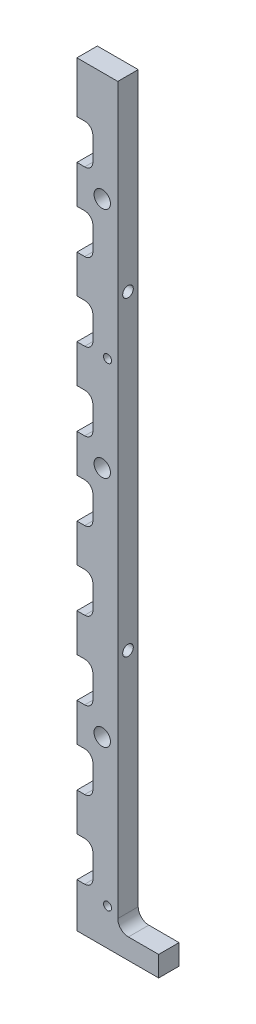
SolidWorks part; units mm, degrees
ref_plane "Front Plane" through (0, 0, 0) normal (0, 0, 1) x (1, 0, 0)
ref_plane "Top Plane" through (0, 0, 0) normal (0, 1, 0) x (1, 0, 0)
ref_plane "Right Plane" through (0, 0, 0) normal (1, 0, 0) x (0, 0, -1)
sketch "Sketch1" plane through (0, 0, 0) normal (0, 0, 1) x (1, 0, 0)
  line L0 (55, 0) -> (-55, 0) construction
  line L1 (-38.1, 0) -> (-50.8, 0)
  line L2 (-38.1, 0) -> (-38.1, 234.95)
  line L3 (-38.1, 234.95) -> (-50.8, 234.95)
  line L4 (-50.8, 0) -> (-50.8, 234.95)
  line L6 (0, -884.6258) -> (0, 49115.3742) construction
  dimension "D1" = 101.6
  dimension "D2" = 12.7
  dimension "D3" = 234.95
extrude "Boss-Extrude1" add sketch "Sketch1" along normal mid plane 6.35
sketch "Sketch2" plane through (0, 0, 0) normal (0, 0, 1) x (1, 0, 0)
  line L0 (-50.8, 234.95) -> (-50.8, 0) construction
  line L1 (-50.8, 26.0782) -> (-45.847, 26.0782)
  line L2 (-50.8, 26.0782) -> (-50.8, 13.7592)
  line L3 (-50.8, 13.7592) -> (-45.847, 13.7592)
  line L4 (-45.847, 26.0782) -> (-45.847, 13.7592)
  line L5 (3.4925, 0) -> (-3.4925, 0) construction
  dimension "D2" = 12.319
  dimension "cable position" = 13.7592
  dimension "D3" = 4.953
extrude "Cut-Extrude1" cut sketch "Sketch2" against normal through all and the other way through all
fillet "Fillet1" radius 2.54 2 edges at (-45.847, 13.7592, 0) (-45.847, 26.0782, 0)
pattern_linear "LPattern3" count 9 spacing 24.13 along (0, 1, 0) of "Cut-Extrude1", "Fillet1"
hole_wizard "M4x0.7 Tapped Hole1" positions "Sketch4" profile "Sketch3" tap size "M4x0.7" standard "ANSI Metric" end condition through all
sketch "Sketch4" plane through (-50.8, 0, 0) normal (-1, 0, 0) x (0, 0, 1)
  line L0 (-3.175, 86.1492) -> (3.175, 74.3382) construction
  line L3 (3.175, 86.1492) -> (-3.175, 74.3382) construction
  line L5 (-3.175, 182.6692) -> (3.175, 170.8582) construction
  line L8 (-3.175, 170.8582) -> (3.175, 182.6692) construction
  line L12 (-3.175, 170.8582) -> (3.175, 170.8582) construction
  line L13 (3.175, 182.6692) -> (3.175, 170.8582) construction
  point P0 (0, 80.2437)
  point P1 (0, 176.7637)
sketch "Sketch3" plane through (-50.8, 80.2437, 0) normal (0, 1, 0) x (0, 0, 1)
  line L0 (0, 0) -> (0, 12.7)
  line L1 (0, 12.7) -> (1.65, 12.7)
  line L2 (1.65, 12.7) -> (1.65, 0)
  line L5 (1.65, 0) -> (0, 0)
  line L11 (0, -6.35) -> (0, 107.95) construction
  dimension "Thru Tap Drill Dia." = 3.3
  dimension "Thru Tap Drill Depth" = 12.7
cosmetic thread "Hole Thread1" parameters "D2"=4
cosmetic thread "Hole Thread2" parameters "D2"=4
sketch "Sketch5" plane through (0, 0, 0) normal (0, 0, 1) x (1, 0, 0)
  line L2 (-38.1, 6.35) -> (-25.4, 6.35)
  line L3 (-25.4, 6.35) -> (-25.4, 0)
  line L4 (-25.4, 0) -> (-38.1, 0)
  line L5 (-38.1, 0) -> (-38.1, 6.35)
  line L6 (-38.1, 0) -> (-38.1, 234.95) construction
  line L7 (0, -981.1026) -> (0, 49018.8974) construction
  line L13 (-50.8, 13.7592) -> (-50.8, 0) construction
  dimension "D1" = 50.8
  dimension "D2" = 6.35
  dimension "D7" = 25.4
extrude "Boss-Extrude2" add sketch "Sketch5" along normal up to surface (3.175 mm away) and the other way up to surface (3.175 mm away) up to face at (-47.9128, 116.5102, 3.175) other way up to face at (-47.9128, 116.5102, -3.175)
ref_axis "Axis1" through (0, 246.6975, 0) along (0, -1, 0)
hole_wizard "M3x0.5 Tapped Hole1" positions "Sketch7" profile "Sketch6" tap size "M3x0.5" standard "ANSI Metric" end condition through all
sketch "Sketch7" plane through (0, 0, 3.175) normal (0, 0, 1) x (1, 0, 0)
  line L2 (-38.1, 6.35) -> (-25.4, 6.35) construction
  line L4 (-38.1, 6.35) -> (-38.1, 234.95) construction
  line L5 (3.4925, 0) -> (-3.4925, 0) construction
  line L6 (-41.275, 11.43) -> (-41.275, 158.75) construction
  point P0 (-41.275, 11.43)
  point P4 (-41.275, 158.75)
  dimension "D1" = 5.08
  dimension "D2" = 3.175
  dimension "D3" = 158.75
sketch "Sketch6" plane through (-41.275, 11.43, 3.175) normal (1, 0, 0) x (0, -1, 0)
  line L0 (0, 0) -> (0, 6.35)
  line L1 (0, 6.35) -> (1.25, 6.35)
  line L2 (1.25, 6.35) -> (1.25, 0)
  line L5 (1.25, 0) -> (0, 0)
  line L11 (0, -6.35) -> (0, 107.95) construction
  dimension "Thru Tap Drill Dia." = 2.5
  dimension "Thru Tap Drill Depth" = 6.35
cosmetic thread "Hole Thread3" parameters "D2"=3
cosmetic thread "Hole Thread4" parameters "D2"=3
fillet "Fillet2" radius 3.302 1 edges
sketch "Sketch8" plane through (0, 0, 3.175) normal (0, 0, 1) x (1, 0, 0)
  line L0 (-50.8, 56.1137) -> (-42.926, 56.1137) construction
  line L1 (-50.8, 62.0192) -> (-50.8, 50.2082) construction
  line L2 (-50.8, 200.8937) -> (-42.926, 200.8937) construction
  line L3 (-50.8, 128.5037) -> (-42.926, 128.5037) construction
  line L4 (-38.1, 9.652) -> (-38.1, 234.95) construction
  line L5 (-50.8, 206.7992) -> (-50.8, 194.9882) construction
  line L6 (-50.8, 134.4092) -> (-50.8, 122.5982) construction
  line L7 (-42.926, 56.1137) -> (-42.926, 128.5037) construction
  line L8 (-42.926, 128.5037) -> (-42.926, 200.8937) construction
  circle A0 centre (-42.926, 200.8937) radius 2.5527
  circle A1 centre (-42.926, 56.1137) radius 2.5527
  circle A2 centre (-42.926, 200.8937) radius 3.8862 construction
  circle A3 centre (-42.926, 56.1137) radius 3.8862 construction
  circle A4 centre (-42.926, 128.5037) radius 2.5527
  circle A5 centre (-42.926, 128.5037) radius 3.8862 construction
  dimension "D1" = 5.1054
  dimension "D2" = 7.7724
  dimension "D3" = 4.826
extrude "Cut-Extrude2" cut sketch "Sketch8" against normal through all
sketch "Sketch9" plane through (0, 0, 3.175) normal (0, 0, 1) x (1, 0, 0)
  line L0 (-50.8, 13.7592) -> (-50.8, 0) construction
  line L1 (-50.8, -1.5875) -> (-25.4, -1.5875)
  line L2 (-50.8, -1.5875) -> (-50.8, 236.5375)
  line L3 (-50.8, 236.5375) -> (-25.4, 236.5375)
  line L4 (-25.4, -1.5875) -> (-25.4, 236.5375)
  line L5 (-50.8, 0) -> (-25.4, 0) construction
  line L6 (-38.1, 234.95) -> (-50.8, 234.95) construction
  dimension "D1" = 25.4
  dimension "D2" = 1.5875
  dimension "D3" = 1.5875
